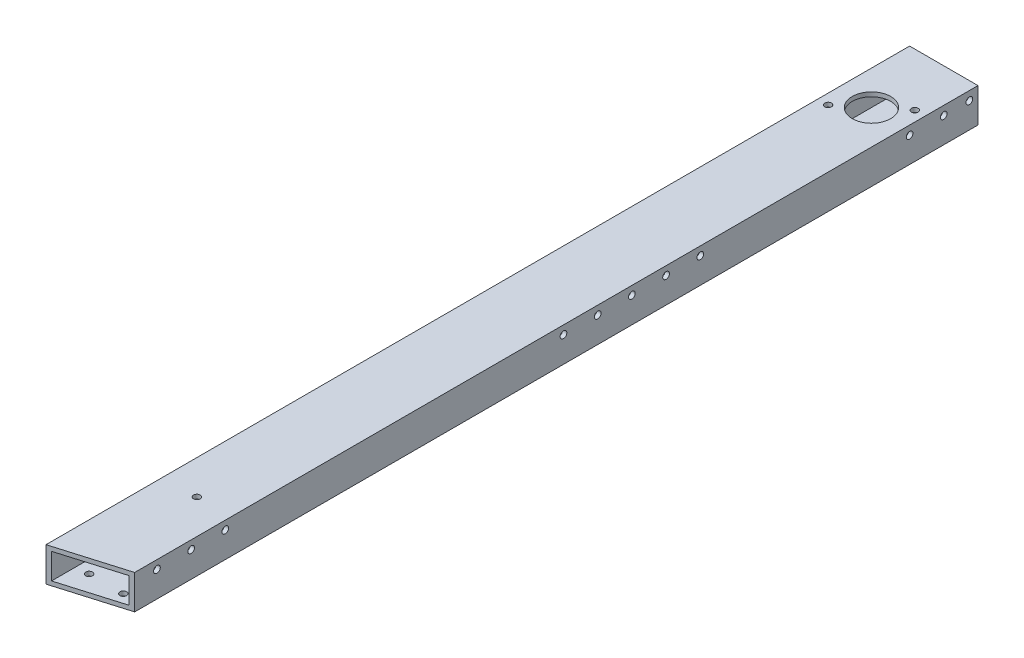
SolidWorks part; units mm, degrees
ref_plane "Front Plane" through (0, 0, 0) normal (0, 0, 1) x (1, 0, 0)
ref_plane "Top Plane" through (0, 0, 0) normal (0, 1, 0) x (1, 0, 0)
ref_plane "Right Plane" through (0, 0, 0) normal (1, 0, 0) x (0, 0, -1)
sketch "Sketch1" plane through (0, 0, 0) normal (0, 0, 1) x (1, 0, 0)
  line L0 (-22.225, 9.525) -> (22.225, 9.525)
  line L2 (-25.4, 12.7) -> (25.4, 12.7)
  line L3 (-25.4, 12.7) -> (-25.4, -12.7)
  line L4 (-25.4, -12.7) -> (25.4, -12.7)
  line L5 (25.4, 12.7) -> (25.4, -12.7)
  line L10 (22.225, 9.525) -> (22.225, -9.525)
  line L11 (-22.225, -9.525) -> (22.225, -9.525)
  line L12 (-22.225, 9.525) -> (-22.225, -9.525)
  point P12 (0, 12.7)
  point P14 (25.4, 0)
  dimension "Wall Thickness" = 3.175
  dimension "Outside Width" = 50.8
  dimension "Outside Height" = 25.4
  dimension "Inside Height" = 19.05
  dimension "Inside Width" = 44.45
sketch "Sketch2" plane through (0, 0, 0) normal (1, 0, 0) x (0, 0, -1)
  line L0 (320.675, 0) -> (-320.675, 0)
  point P4 (0, 0)
  point P7 (-320.675, 0)
  point P10 (320.675, 0)
  dimension "Length" = 641.35
sketch "Sketch3" plane through (0, 0, 0) normal (0, 0, 1) x (1, 0, 0)
  line L21 (25.4, 12.7) -> (-25.4, 12.7)
  line L22 (25.4, -12.7) -> (25.4, 12.7)
  line L23 (-25.4, -12.7) -> (25.4, -12.7)
  line L24 (-25.4, 12.7) -> (-25.4, -12.7)
  line L25 (25.4, 12.7) -> (-25.4, 12.7)
  line L26 (25.4, -12.7) -> (25.4, 12.7)
  line L27 (-25.4, -12.7) -> (25.4, -12.7)
  line L28 (-25.4, 12.7) -> (-25.4, -12.7)
  line L29 (22.225, 9.525) -> (-22.225, 9.525)
  line L30 (22.225, -9.525) -> (22.225, 9.525)
  line L31 (-22.225, -9.525) -> (22.225, -9.525)
  line L32 (-22.225, 9.525) -> (-22.225, -9.525)
  line L33 (22.225, 9.525) -> (-22.225, 9.525)
  line L34 (22.225, -9.525) -> (22.225, 9.525)
  line L35 (-22.225, -9.525) -> (22.225, -9.525)
  line L36 (-22.225, 9.525) -> (-22.225, -9.525)
  dimension "D1" = 0
  dimension "D2" = 0
extrude "Boss-Extrude1" add sketch "Sketch3" along normal up to vertex (320.675 mm away) and the other way up to vertex (320.675 mm away) up to point (0, 0, 320.675) other way up to point (0, 0, -320.675)
sketch "Drawing Reference" plane through (0, 0, 0) normal (1, 0, 0) x (0, 0, -1)
  line L0 (-320.675, 0) -> (320.675, 0) construction
  line L1 (0, -12.7) -> (0, 12.7) construction
  line L2 (-320.675, -12.7) -> (320.675, -12.7) construction
  line L5 (-320.675, 12.7) -> (320.675, 12.7) construction
  point P7 (-284.099, 0)
  point P8 (284.099, 0)
  dimension "D1" = 36.576
sketch "Sketch4" plane through (0, 12.7, 0) normal (0, 1, 0) x (1, 0, 0)
  line L0 (-25.4, -320.675) -> (25.4, -305.6274)
  line L1 (25.4, -320.675) -> (25.4, 320.675) construction
  line L2 (25.4, -320.675) -> (-25.4, -320.675)
  dimension "D1" = 16.5
extrude "Cut-Extrude1" cut sketch "Sketch4" against normal through all and the other way through all flip side to cut
sketch "Sketch8" plane through (0, 12.7, 0) normal (0, 1, 0) x (1, 0, 0)
  line L0 (0, 320.675) -> (0, 266.954) construction
  line L1 (25.4, 320.675) -> (-25.4, 320.675) construction
  circle A0 centre (0, 266.954) radius 14.2875
  dimension "D1" = 53.721
extrude "Cut-Extrude2" cut sketch "Sketch8" against normal through all
sketch "Sketch9" plane through (0, -12.7, 0) normal (0, -1, 0) x (1, 0, 0)
  line L0 (-12.7762, 284.753) -> (-12.7762, 301.263) construction
  line L1 (-12.7762, 301.263) -> (12.6238, 301.263) construction
  line L2 (12.6238, 301.263) -> (12.6238, 284.753) construction
  line L3 (12.6238, 284.753) -> (-12.7762, 284.753) construction
hole_wizard "#10 Clearance Hole1" positions "Sketch10" profile "Sketch11" hole size "#10" standard "ANSI Inch"
sketch "Sketch10" plane through (0, -12.7, 0) normal (0, -1, 0) x (-1, 0, 0)
  point P0 (-12.6238, -284.753)
  point P3 (12.7762, -284.753)
  point P6 (12.7762, -301.263)
  point P9 (-12.6238, -301.263)
sketch "Sketch11" plane through (12.6238, -12.7, 284.753) normal (1, 0, 0) x (0, 0, -1)
  line L0 (0, 0) -> (0, 6.5757)
  line L1 (0, 6.5757) -> (2.4892, 5.08)
  line L2 (2.4892, 5.08) -> (2.4892, 0)
  line L5 (2.4892, 0) -> (0, 0)
  line L10 (0, 6.5757) -> (-2.4892, 5.08) construction
  line L11 (0, -6.35) -> (0, 107.95) construction
  dimension "Hole Dia." = 4.9784
  dimension "Hole Depth" = 5.08
  dimension "Drill Angle" = 118
sketch "Sketch12" plane through (25.4, 0, 0) normal (1, 0, 0) x (0, 0, -1)
  line L0 (320.675, 533.4) -> (-305.6274, 533.4) construction
  line L1 (320.675, 520.7) -> (320.675, 546.1) construction
  line L2 (-305.6274, 546.1) -> (-305.6274, 520.7) construction
hole_wizard "#10 Clearance Hole2" positions "Sketch13" profile "Sketch14" hole size "#10" standard "ANSI Inch"
sketch "Sketch13" plane through (25.4, 0, 0) normal (1, 0, 0) x (0, 0, -1)
  point P0 (314.2868, 6.1483)
  point P3 (295.2368, 6.1483)
  point P6 (269.875, 6.1483)
sketch "Sketch14" plane through (25.4, 6.1483, -314.2868) normal (0, 1, 0) x (0, 0, -1)
  line L0 (0, 0) -> (0, 4.7977)
  line L1 (0, 4.7977) -> (2.4892, 3.302)
  line L2 (2.4892, 3.302) -> (2.4892, 0)
  line L5 (2.4892, 0) -> (0, 0)
  line L10 (0, 4.7977) -> (-2.4892, 3.302) construction
  line L11 (0, -6.35) -> (0, 107.95) construction
  dimension "Hole Dia." = 4.9784
  dimension "Hole Depth" = 3.302
  dimension "Drill Angle" = 118
hole_wizard "#10 Clearance Hole3" positions "Sketch15" profile "Sketch16" hole size "#10" standard "ANSI Inch" end condition through all
sketch "Sketch15" plane through (25.4, 0, 0) normal (1, 0, 0) x (0, 0, -1)
  point P0 (114.427, 6.35)
  point P3 (89.027, 6.35)
  point P6 (63.627, 6.35)
  point P9 (38.227, 6.35)
  point P12 (12.827, 6.35)
  point P24 (-289.0885, 6.3882)
  point P27 (-263.6885, 6.3882)
  point P30 (-238.3267, 6.3882)
sketch "Sketch16" plane through (25.4, 6.35, -114.427) normal (0, 1, 0) x (0, 0, -1)
  line L0 (0, 0) -> (0, 50.8)
  line L1 (0, 50.8) -> (2.4892, 50.8)
  line L2 (2.4892, 50.8) -> (2.4892, 0)
  line L5 (2.4892, 0) -> (0, 0)
  line L11 (0, -6.35) -> (0, 107.95) construction
  dimension "Thru Hole Dia." = 4.9784
  dimension "Thru Hole Depth" = 50.8
sketch "Sketch18" plane through (0, 12.7, 0) normal (0, 1, 0) x (1, 0, 0)
  line L0 (17.786, 281.371) -> (-17.786, 252.537) construction
hole_wizard "#10 Clearance Hole4" positions "Sketch19" profile "Sketch20" hole size "#10" standard "ANSI Inch" end condition through all
sketch "Sketch19" plane through (0, 12.7, 0) normal (0, 1, 0) x (1, 0, 0)
  point P0 (-17.786, 252.537)
  point P3 (17.786, 281.371)
sketch "Sketch20" plane through (-17.786, 12.7, -252.537) normal (1, 0, 0) x (0, 0, 1)
  line L0 (0, 0) -> (0, 25.4)
  line L1 (0, 25.4) -> (5.2197, 25.4)
  line L2 (2.4892, 22.2589) -> (2.4892, 0)
  line L5 (2.4892, 0) -> (0, 0)
  line L7 (5.2197, 25.4) -> (2.4892, 22.2589)
  line L8 (-5.2197, 25.4) -> (-2.4892, 22.2589) construction
  line L11 (0, -6.35) -> (0, 107.95) construction
  dimension "Thru Hole Dia." = 4.9784
  dimension "Thru Hole Depth" = 25.4
  dimension "Far C'Sink Dia." = 10.4394
  dimension "Far C'Sink Angle" = 82
sketch "Sketch21" plane through (0, 12.7, 0) normal (0, 1, 0) x (1, 0, 0)
  line L0 (-0.0762, -284.753) -> (-0.0762, -233.953) construction
  line L1 (12.6238, -284.753) -> (-12.7762, -284.753) construction
  dimension "D1" = 50.8
hole_wizard "#10 Clearance Hole5" positions "Sketch22" profile "Sketch23" hole size "#10" standard "ANSI Inch" end condition through all
sketch "Sketch22" plane through (0, 12.7, 0) normal (0, 1, 0) x (1, 0, 0)
  point P0 (-0.0762, -233.953)
sketch "Sketch23" plane through (-0.0762, 12.7, 233.953) normal (1, 0, 0) x (0, 0, 1)
  line L0 (0, 0) -> (0, 25.4)
  line L1 (0, 25.4) -> (2.4892, 25.4)
  line L2 (2.4892, 25.4) -> (2.4892, 0)
  line L5 (2.4892, 0) -> (0, 0)
  line L11 (0, -6.35) -> (0, 107.95) construction
  dimension "Thru Hole Dia." = 4.9784
  dimension "Thru Hole Depth" = 25.4
equation "\"D1@Drawing Reference\"=\"Outside Width@Sketch1\" * 0.72"
